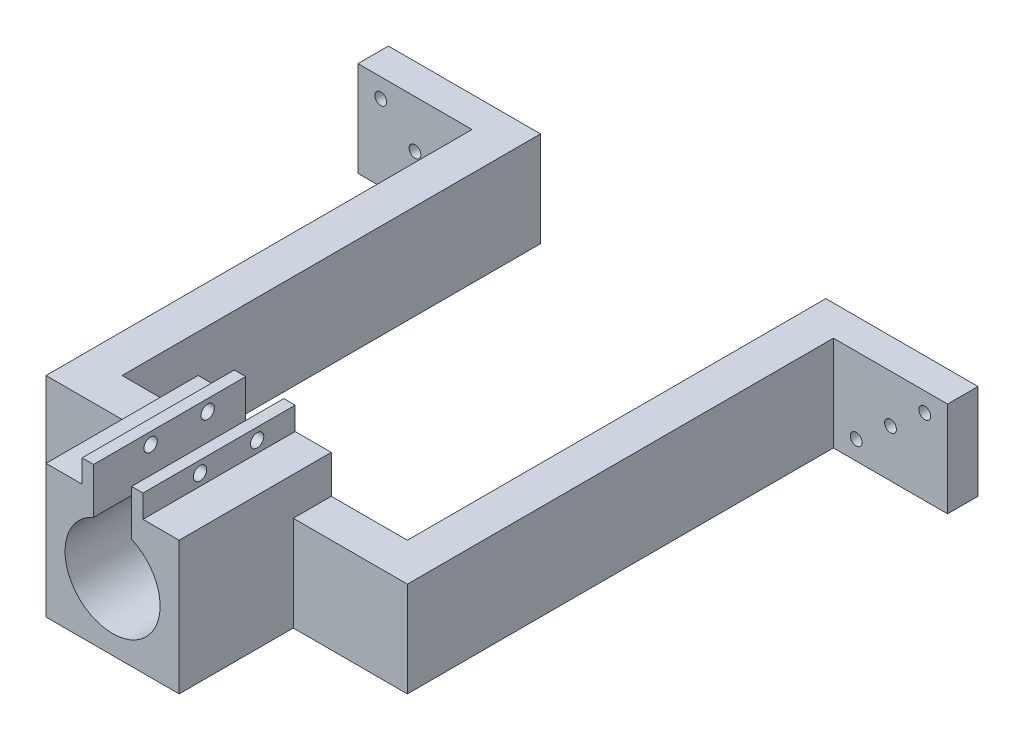
SolidWorks part; units mm, degrees
note: The reader was unsure of these and kept them because the rebuilt part matched: shared geometry of "Sketch1<3>", "Sketch1<5>", "Sketch1<8>".
ref_plane "Front Plane" through (0, 0, 0) normal (0, 0, 1) x (1, 0, 0)
ref_plane "Top Plane" through (0, 0, 0) normal (0, 1, 0) x (1, 0, 0)
ref_plane "Right Plane" through (0, 0, 0) normal (1, 0, 0) x (0, 0, -1)
sketch "Sketch1" plane through (0, 0, 0) normal (0, 0, 1) x (1, 0, 0)
  line L0 (5, 0) -> (-5, 0)
  line L1 (-17.5, -17.5) -> (17.5, -17.5)
  line L2 (-17.5, -17.5) -> (-17.5, 17.5)
  line L3 (-17.5, 17.5) -> (17.5, 17.5)
  line L4 (17.5, -17.5) -> (17.5, 17.5)
  line L5 (-17.5, -17.5) -> (17.5, 17.5) construction
  line L6 (-17.5, 17.5) -> (17.5, -17.5) construction
  line L7 (5, 0) -> (5, 30)
  line L8 (-5, 0) -> (-5, 30)
  line L9 (5, 30) -> (-5, 30)
  line L10 (17.5, -17.5) -> (17.5, 7.5)
  line L11 (-5, 17.5) -> (-8, 17.5)
  line L12 (-5, 17.5) -> (-5, 23.5)
  line L13 (-5, 23.5) -> (-8, 23.5)
  line L14 (-8, 17.5) -> (-8, 23.5)
  line L15 (5, 17.5) -> (8, 17.5)
  line L16 (5, 17.5) -> (5, 23.5)
  line L17 (5, 23.5) -> (8, 23.5)
  line L18 (8, 17.5) -> (8, 23.5)
  line L19 (17.5, -17.5) -> (47.5, -17.5)
  line L20 (17.5, 7.5) -> (47.5, 7.5)
  line L21 (47.5, -17.5) -> (47.5, 7.5)
  line L22 (-32.5, 7.5) -> (-32.5, -17.5) construction
  line L23 (-17.5, -17.5) -> (-17.5, 7.5)
  line L24 (-17.5, -17.5) -> (-47.5, -17.5)
  line L25 (-17.5, 7.5) -> (-47.5, 7.5)
  line L26 (77.5, 7.5) -> (47.5, -17.5) construction
  line L27 (-17.5, -17.5) -> (-47.5, -17.5)
  line L28 (-17.5, -17.5) -> (-17.5, 7.5)
  line L29 (-17.5, 7.5) -> (-47.5, 7.5)
  line L30 (-47.5, -17.5) -> (-47.5, 7.5)
  line L31 (37.5, 7.5) -> (37.5, -17.5)
  line L32 (47.5, -17.5) -> (77.5, -17.5)
  line L33 (47.5, -17.5) -> (47.5, 7.5)
  line L34 (47.5, 7.5) -> (77.5, 7.5)
  line L35 (77.5, -17.5) -> (77.5, 7.5)
  line L36 (-37.5, 7.5) -> (-37.5, -17.5)
  line L37 (-47.5, -17.5) -> (-77.5, -17.5)
  line L38 (-47.5, -17.5) -> (-47.5, 7.5)
  line L39 (-47.5, 7.5) -> (-77.5, 7.5)
  line L40 (-77.5, -17.5) -> (-77.5, 7.5)
  line L41 (-77.5, 7.5) -> (-47.5, -17.5) construction
  circle A0 centre (0, 0) radius 12.5
  circle A1 centre (-53.5, -12.5) radius 1.55
  circle A2 centre (53.5, -12.5) radius 1.55
  circle A3 centre (71.5, 2.5) radius 1.55
  circle A4 centre (-71.5, 2.5) radius 1.55
  circle A5 centre (-62.5, -5) radius 1.55
  circle A6 centre (62.5, -5) radius 1.55
  point P0 (0, 0)
  point P32 (-32.5, -5)
  dimension "D1" = 25
  dimension "D23" = 3.1
  dimension "D2" = 35
  dimension "D3" = 35
  dimension "D4" = 10
  dimension "D5" = 30
  dimension "D6" = 3
  dimension "D7" = 3
  dimension "D8" = 6
  dimension "D9" = 6
  dimension "D10" = 25
  dimension "D11" = 30
  dimension "D12" = 30
  dimension "D13" = 25
  dimension "D14" = 30
  dimension "D16" = 6
  dimension "D17" = 30
  dimension "D19" = 6
  dimension "D20" = 10
  dimension "D21" = 10
  dimension "D22" = 6
  dimension "D24" = 6
extrude "Boss-Extrude1" add sketch "Sketch1" along normal blind 40 contours A0 L8 L3 L2 L1 L4 L7 | L14 L3 L8 L13 | L3 L18 L17 L7
sketch "Sketch2" plane through (8, 0, 0) normal (1, 0, 0) x (0, 0, -1)
  line L0 (-25, 23.5) -> (-25, 17.5) construction
  line L1 (-40, 23.5) -> (0, 23.5) construction
  line L2 (-40, 17.5) -> (0, 17.5) construction
  line L3 (-40, 17.5) -> (-40, 23.5) construction
  circle A0 centre (-25, 20.5) radius 1.75
  circle A1 centre (-10, 20.5) radius 1.75
  dimension "D1" = 3.5
  dimension "D2" = 3.5
  dimension "D3" = 15
  dimension "D4" = 15
extrude "Cut-Extrude1" cut sketch "Sketch2" against normal blind 20
extrude "Boss-Extrude2" add sketch "Sketch1<3>" along normal blind 10 contours L40 L24 L2 L25 | L19 L21 L20 L4 | L36 L29 L30 L27 | L20 L31 L19 L21
sketch "Sketch1<3>" plane through (0, 0, 0) normal (0, 0, 1) x (1, 0, 0) same geometry as "Sketch1"
extrude "Boss-Extrude3" add sketch "Sketch1<5>" against normal blind 110 contours L36 L29 L30 L27 | L20 L31 L19 L21
sketch "Sketch1<5>" plane through (0, 0, 0) normal (0, 0, 1) x (1, 0, 0) same geometry as "Sketch1"
extrude "Boss-Extrude8" add sketch "Sketch1<8>" along normal blind 8 from offset 110 contours L32 L35 L34 L21 A2 | L40 L37 L30 L39 A1
sketch "Sketch1<8>" plane through (0, 0, 0) normal (0, 0, 1) x (1, 0, 0) same geometry as "Sketch1"
